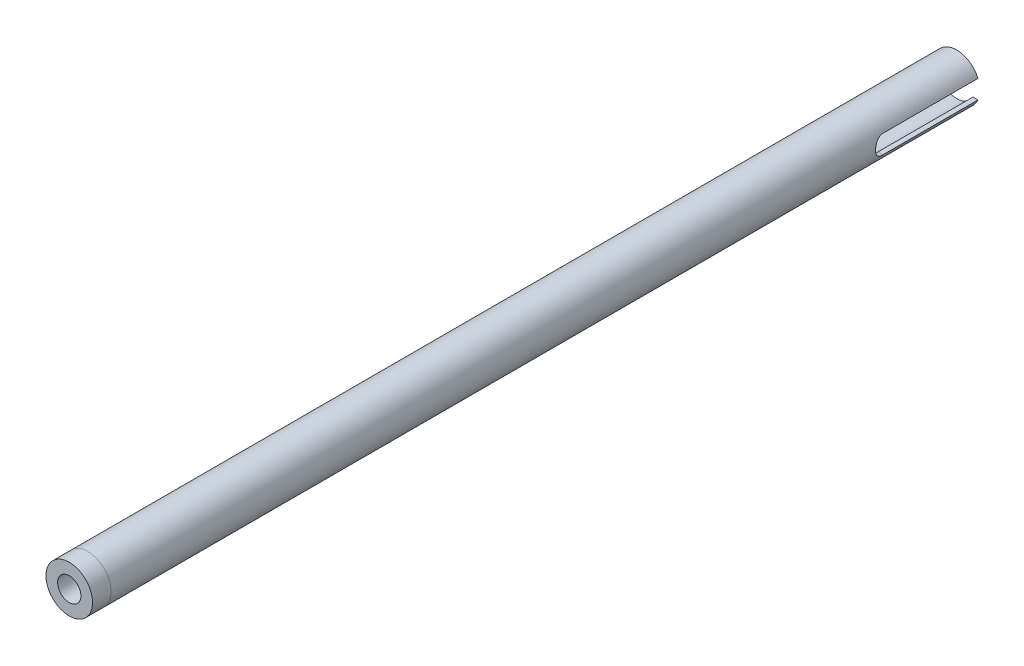
SolidWorks part; units mm, degrees
ref_plane "Front Plane" through (0, 0, 0) normal (0, 0, 1) x (1, 0, 0)
ref_plane "Top Plane" through (0, 0, 0) normal (0, 1, 0) x (1, 0, 0)
ref_plane "Right Plane" through (0, 0, 0) normal (1, 0, 0) x (0, 0, -1)
sketch "Axis" plane through (0, 0, 0) normal (0, 1, 0) x (1, 0, 0)
  line L0 (0, 0) -> (0, 302.3692) construction
  line L1 (0, 0) -> (0, -28.575) construction
  line L2 (0, 302.3692) -> (-7.9375, 302.3692) construction
  line L3 (0, 325.6526) -> (-31.298, 233.8452) construction
  dimension "D1" = 28.575
  dimension "D2" = 7.9375
sketch "Sketch1" plane through (0, 0, 0) normal (0, 0, 1) x (1, 0, 0)
  line L0 (-7.9375, 0) -> (7.9375, 0) construction
  line L1 (-7.2748, 3.175) -> (7.2748, 3.175)
  line L2 (-7.2748, -3.175) -> (7.2748, -3.175)
  circle A0 centre (0, 0) radius 7.9375
  circle A1 centre (0, 0) radius 6.4135
  circle A2 centre (0, 0) radius 3.9688
  dimension "D1" = 15.875
  dimension "D3" = 7.9375
  dimension "D2" = 1.524
  dimension "D4" = 6.35
extrude "Threaded insert 1-1" add sketch "Sketch1" against normal blind 6.35 contours A2 L1 A1 | A1 L1 A0 | A2 L0 A1 L1 | A1 L0 A0 L1 | L0 A1 L2 A0 | L0 A2 L2 A1 | A2 L2 A1 | A1 L2 A0 | L0 A1 L2 A2 | L0 A0 L2 A1 | A0 L0 A1 L1 | A1 L0 A2 L1 region at (4.7887, 1.6543, 0) region at (4.7887, -1.6543, 0) region at (6.9234, 1.6163, 0) region at (6.9234, -1.6163, 0) region at (-4.7887, -1.6543, 0) region at (-4.7887, 1.6543, 0) region at (0, 4.6159, 0) region at (0, -4.6159, 0) region at (0, 6.5666, 0) region at (6.4237, -3.3281, 0) region at (-6.9234, -1.6163, 0) region at (-6.9234, 1.6163, 0)
extrude "Threaded insert 1-2" add sketch "Sketch1<3>" against normal blind 9.525 from surface contours A2 L1 A1 | A2 L0 A1 L1 | L0 A2 L2 A1 | A2 L2 A1 | L0 A1 L2 A2 | A1 L0 A2 L1 region at (4.7887, 1.6543, 0) region at (4.7887, -1.6543, 0) region at (-4.7887, -1.6543, 0) region at (-4.7887, 1.6543, 0) region at (0, 4.6159, 0) region at (0, -4.6159, 0) starting at face at (7.9375, 0, -6.35)
sketch "Sketch1<3>" plane through (0, 0, 0) normal (0, 0, 1) x (1, 0, 0) same geometry as "Sketch1"
extrude "A-arm tube" add sketch "Sketch1<4>" against normal up to vertex (302.3692 mm away) from surface separate body contours A1 L1 A0 | A1 L0 A0 L1 | L0 A1 L2 A0 | A1 L2 A0 | L0 A0 L2 A1 | A0 L0 A1 L1 region at (6.9234, 1.6163, 0) region at (6.9234, -1.6163, 0) region at (0, 6.5666, 0) region at (6.4237, -3.3281, 0) region at (-6.9234, -1.6163, 0) region at (-6.9234, 1.6163, 0) up to point (0, 0, -302.3692) starting at face at (6.4135, 0, -6.35)
sketch "Sketch1<4>" plane through (0, 0, 0) normal (0, 0, 1) x (1, 0, 0) same geometry as "Sketch1"
extrude "Apex slot" cut sketch "Sketch1<5>" along normal blind 35.56 from surface contours A0 L0 A1 L1 | L0 A0 L2 A1 | A1 L0 A0 L1 | L0 A1 L2 A0 region at (6.9234, 1.6163, 0) region at (6.9234, -1.6163, 0) region at (-6.9234, -1.6163, 0) region at (-6.9234, 1.6163, 0) starting at face at (6.4135, 0, -302.3692)
sketch "Sketch1<5>" plane through (0, 0, 0) normal (0, 0, 1) x (1, 0, 0) same geometry as "Sketch1"
fillet "Fillet1" radius 3.175 4 edges at (-6.4237, 3.175, -266.8092) (-6.4237, -3.175, -266.8092) (6.4237, -3.175, -266.8092) (6.4237, 3.175, -266.8092)
equation "\"tube diameter\"= 5 / 8"
equation "\"tube thickness\"= .06"
equation "\"apex thickness\"= .25"
equation "\"tube slot\"= 1.4"
equation "\"D1@Sketch1\"=\"tube diameter\""
equation "\"D2@Sketch1\"=\"tube thickness\""
equation "\"threaded insert hole\"= .3125"
equation "\"D3@Sketch1\"=\"threaded insert hole\""
equation "\"D4@Sketch1\"=\"apex thickness\""
equation "\"D1@Apex slot\" = \"tube slot\""
equation "\"D1@Fillet1\"=\"apex thickness\"/2"
equation "\"D2@Axis\"=\"tube diameter\"/2"
